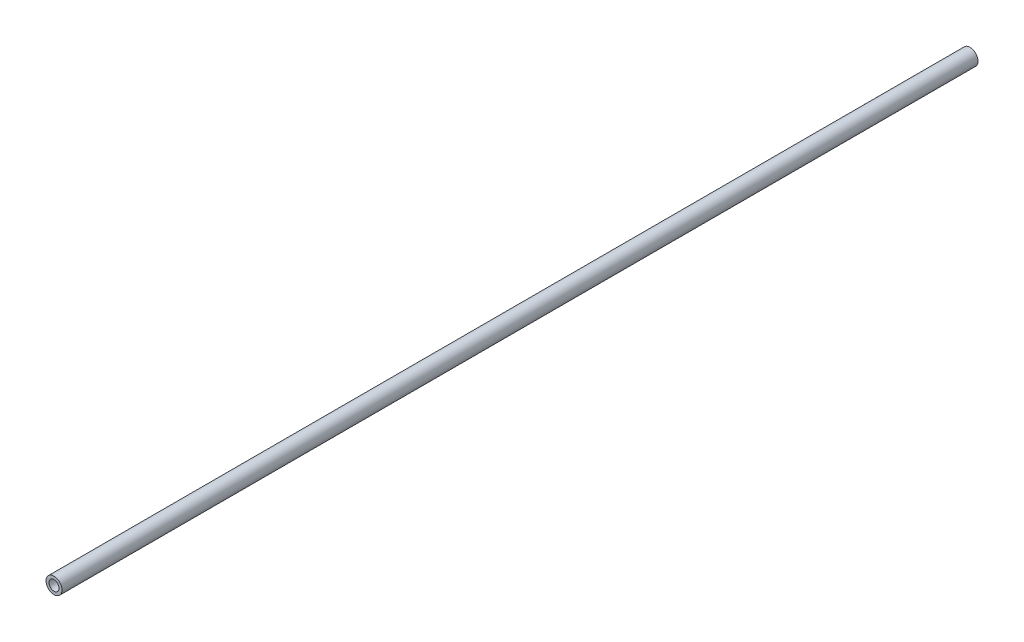
SolidWorks part; units mm, degrees
ref_plane "Front Plane" through (0, 0, 0) normal (0, 0, 1) x (1, 0, 0)
ref_plane "Top Plane" through (0, 0, 0) normal (0, 1, 0) x (1, 0, 0)
ref_plane "Right Plane" through (0, 0, 0) normal (1, 0, 0) x (0, 0, -1)
sketch "Sketch1" plane through (0, 0, 0) normal (0, 0, 1) x (1, 0, 0)
  circle A0 centre (0, 0) radius 2.3876
  circle A1 centre (0, 0) radius 1.4986
  dimension "D1" = 4.7752
  dimension "D2" = 2.9972
extrude "Boss-Extrude1" add sketch "Sketch1" along normal blind 273.05
